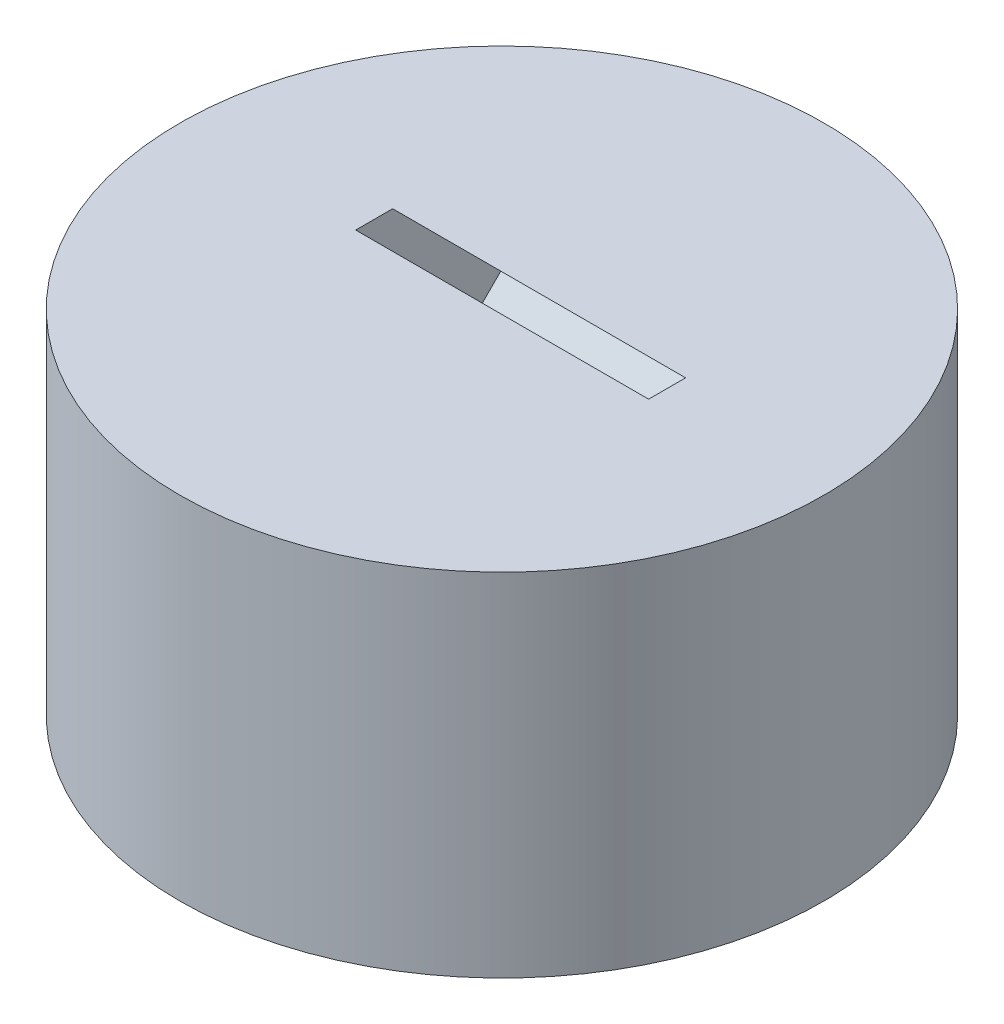
SolidWorks part; units mm, degrees
ref_plane "Front Plane" through (0, 0, 0) normal (0, 0, 1) x (1, 0, 0)
ref_plane "Top Plane" through (0, 0, 0) normal (0, 1, 0) x (1, 0, 0)
ref_plane "Right Plane" through (0, 0, 0) normal (1, 0, 0) x (0, 0, -1)
sketch "Sketch1" plane through (0, 0, 0) normal (0, 1, 0) x (1, 0, 0)
  circle A0 centre (0, 0) radius 5.5
  dimension "D1" = 11
extrude "Boss-Extrude1" add sketch "Sketch1" along normal blind 6
sketch "Sketch2" plane through (0, 6, 0) normal (0, 1, 0) x (1, 0, 0)
  line L0 (-5.5, 0) -> (5.5, 0) construction
  circle A0 centre (0, 0) radius 5.5 construction
ref_plane "Plane1" through (0, 3, 3) normal (0, 0.7071, 0.7071) x (1, 0, 0)
sketch "Sketch3" plane through (0, 3, 3) normal (0, 0.7071, 0.7071) x (1, 0, 0)
  line L0 (0, 8.1317) -> (0.0836, 4.6325) construction
  line L1 (-2.4164, 4.1863) -> (2.5836, 4.1863)
  line L2 (-2.4164, 4.1863) -> (-2.4164, 4.6325)
  line L3 (-2.4164, 4.6325) -> (2.5836, 4.6325)
  line L4 (2.5836, 4.1863) -> (2.5836, 4.6325)
  ellipse E0 centre (0, 4.2426) end of major axis (5.5, 4.2426) minor radius 3.8891 construction
  dimension "D1" = 5
extrude "Cut-Extrude1" cut sketch "Sketch3" against normal blind 3 and the other way blind 3
